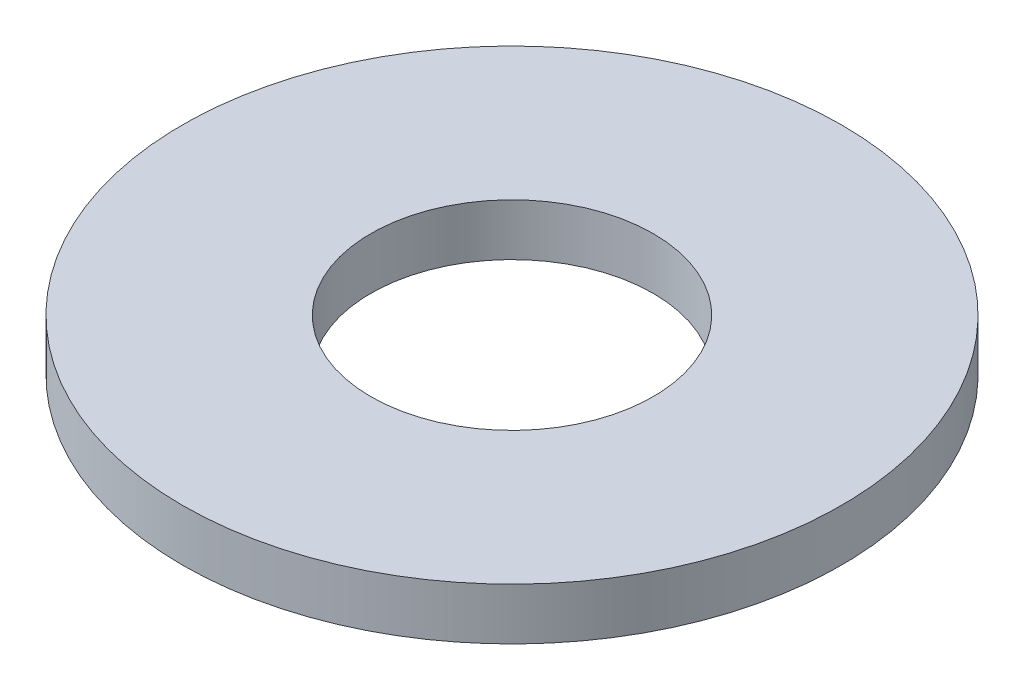
SolidWorks part; units mm, degrees
ref_plane "Front Plane" through (0, 0, 0) normal (0, 0, 1) x (1, 0, 0)
ref_plane "Top Plane" through (0, 0, 0) normal (0, 1, 0) x (1, 0, 0)
ref_plane "Right Plane" through (0, 0, 0) normal (1, 0, 0) x (0, 0, -1)
sketch "Sketch1" plane through (0, 0, 0) normal (0, 1, 0) x (1, 0, 0)
  circle A0 centre (0, 0) radius 70
  dimension "FLANGE_OD" = 140
extrude "Boss-Extrude1" add sketch "Sketch1" along normal blind 11
sketch "Sketch2" plane through (0, 0, 0) normal (0, 1, 0) x (1, 0, 0)
  circle A0 centre (0, 0) radius 30
  dimension "BORE_D" = 60
extrude "Cut-Extrude1" cut sketch "Sketch2" along normal through all
sketch "Sketch3" plane through (0, 11, 0) normal (0, 1, 0) x (1, 0, 0)
  circle A0 centre (0, 0) radius 21.3996 construction
  circle A1 centre (-21.3996, 0) radius 7.161
  dimension "BOLT_D" = 14.3219
  dimension "BOLT_PCD" = 42.7993
extrude "Cut-Extrude2" cut sketch "Sketch3" against normal blind 7.0141 rebuild error yes
pattern_circular "CirPattern1" count 3 over 360 rebuild error yes
